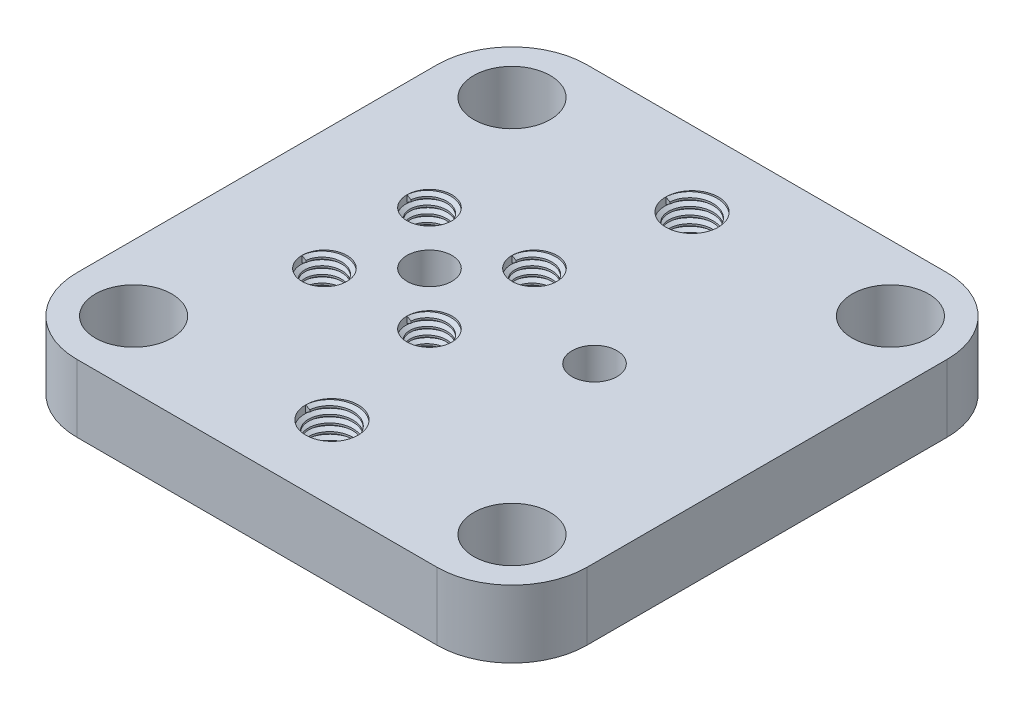
SolidWorks part; units mm, degrees
ref_plane "Front Plane" through (0, 0, 0) normal (0, 0, 1) x (1, 0, 0)
ref_plane "Top Plane" through (0, 0, 0) normal (0, 1, 0) x (1, 0, 0)
ref_plane "Right Plane" through (0, 0, 0) normal (1, 0, 0) x (0, 0, -1)
sketch "Sketch1" plane through (0, 0, 0) normal (0, 1, 0) x (1, 0, 0)
  line L3 (0, 29) -> (0, -29)
  line L4 (0, 0) -> (-29, 0)
  line L5 (-29, -19) -> (-29, 19)
  line L6 (-19, 29) -> (19, 29)
  line L7 (-19, -29) -> (19, -29)
  line L8 (29, -19) -> (29, 19)
  arc A0 (-19, -29) -> (-29, -19) centre (-19, -19) cw
  arc A1 (-29, 19) -> (-19, 29) centre (-19, 19) cw
  arc A2 (19, -29) -> (29, -19) centre (19, -19) ccw
  arc A3 (29, 19) -> (19, 29) centre (19, 19) ccw
  point P4 (0, 0)
  point P9 (-29, -29)
  point P13 (-29, 29)
  dimension "D2" = 10
  dimension "D1" = 29
extrude "Boss-Extrude1" add sketch "Sketch1" along normal blind 9 contours L8 A3 L6 L3 L7 A2 | A0 L7 L3 L4 L5 | A1 L5 L4 L3 L6 region at (14.1788, 0, 0) region at (-14.1788, 0, -14.1788) region at (-14.1788, 0, 14.1788)
sketch "Sketch2" plane through (0, 9, 0) normal (0, 1, 0) x (1, 0, 0)
  line L1 (0, 29) -> (0, 24)
  line L3 (0, 21) -> (-21, 21)
  line L4 (0, 0) -> (0, 21)
  line L5 (0, 0) -> (-4, 0)
  line L10 (-19, 29) -> (19, 29) construction
  circle A0 centre (-11, 0) radius 3
  circle A1 centre (-21, 21) radius 3.5
  circle A2 centre (-21, -21) radius 3.5
  circle A3 centre (21, -21) radius 3.5
  circle A4 centre (21, 21) radius 3.5
  circle A5 centre (11, 0) radius 3
  circle A6 centre (-18, 7) radius 3
  circle A7 centre (-4, 7) radius 3
  circle A8 centre (-18, -7) radius 3
  circle A9 centre (-4, -7) radius 3
  circle A10 centre (0, 24) radius 3.5
  circle A11 centre (0, -24) radius 3.5
  point P4 (0, 0)
  point P10 (0, 29)
  point P12 (0, 21)
  point P23 (-4, 7)
  point P24 (-18, 7)
  point P28 (-4, 0)
extrude "Cut-Extrude1" cut sketch "Sketch2" against normal blind 9 contours A5 | L4 A10 L3 | A9 | A0 | A7 | A6 | A8 | A11 region at (0.011, 9, -24.0516) region at (-11, 9, 0) region at (11, 9, 0) region at (-18, 9, -7) region at (-4, 9, -7) region at (-18, 9, 7) region at (-4, 9, 7)
sketch "Sketch10" plane through (0, 9, 0) normal (0, 1, 0) x (1, 0, 0)
  circle A0 centre (0, 24) radius 3.5
extrude "Cut-Extrude2" cut sketch "Sketch10" against normal blind 9
thread "Thread3" pitch 1 method extrude profile "Thread Profile5" start angle 0, offset 0, length 8, pitch 1, diameter 6
ref_plane "Plane8" through (-7, 9, -7) normal (0, 0, 1) x (-1, 0, 0)
sketch "Thread Profile5" plane through (-7, 9, -7) normal (0, 0, 1) x (-1, 0, 0)
  line L0 (0, 0) -> (0, 1) construction
  line L11 (0, 0) -> (0, 0.875)
  line L12 (0, 0.875) -> (-0.5413, 0.5625)
  line L13 (-0.5413, 0.5625) -> (-0.5413, 0.3125)
  line L15 (-0.5413, 0.3125) -> (0, 0)
  line L17 (-0.5413, 0.4375) -> (0, 0.4375) construction
  point P2 (0, 0)
  dimension "Pitch" = 1
  dimension "Profile_Angle" = 60
  dimension "Profile_Land" = 0.25
  dimension "Profile_Height" = 0.5413
thread "Thread4" pitch 1 method extrude profile "Thread Profile6" start angle 0, offset 0, length 8, pitch 1, diameter 6
ref_plane "Plane9" through (-21, 9, -7) normal (0, 0, 1) x (-1, 0, 0)
sketch "Thread Profile6" plane through (-21, 9, -7) normal (0, 0, 1) x (-1, 0, 0)
  line L0 (0, 0) -> (0, 1) construction
  line L11 (0, 0) -> (0, 0.875)
  line L12 (0, 0.875) -> (-0.5413, 0.5625)
  line L13 (-0.5413, 0.5625) -> (-0.5413, 0.3125)
  line L15 (-0.5413, 0.3125) -> (0, 0)
  line L17 (-0.5413, 0.4375) -> (0, 0.4375) construction
  point P2 (0, 0)
  dimension "Pitch" = 1
  dimension "Profile_Angle" = 60
  dimension "Profile_Land" = 0.25
  dimension "Profile_Height" = 0.5413
thread "Thread5" pitch 1 method extrude profile "Thread Profile7" start angle 0, offset 0, length 8, pitch 1, diameter 6
ref_plane "Plane10" through (-21, 9, 7) normal (0, 0, 1) x (-1, 0, 0)
sketch "Thread Profile7" plane through (-21, 9, 7) normal (0, 0, 1) x (-1, 0, 0)
  line L0 (0, 0) -> (0, 1) construction
  line L11 (0, 0) -> (0, 0.875)
  line L12 (0, 0.875) -> (-0.5413, 0.5625)
  line L13 (-0.5413, 0.5625) -> (-0.5413, 0.3125)
  line L15 (-0.5413, 0.3125) -> (0, 0)
  line L17 (-0.5413, 0.4375) -> (0, 0.4375) construction
  point P2 (0, 0)
  dimension "Pitch" = 1
  dimension "Profile_Angle" = 60
  dimension "Profile_Land" = 0.25
  dimension "Profile_Height" = 0.5413
thread "Thread6" pitch 1 method extrude profile "Thread Profile8" start angle 0, offset 0, length 8, pitch 1, diameter 6
ref_plane "Plane11" through (-7, 9, 7) normal (0, 0, 1) x (-1, 0, 0)
sketch "Thread Profile8" plane through (-7, 9, 7) normal (0, 0, 1) x (-1, 0, 0)
  line L0 (0, 0) -> (0, 1) construction
  line L11 (0, 0) -> (0, 0.875)
  line L12 (0, 0.875) -> (-0.5413, 0.5625)
  line L13 (-0.5413, 0.5625) -> (-0.5413, 0.3125)
  line L15 (-0.5413, 0.3125) -> (0, 0)
  line L17 (-0.5413, 0.4375) -> (0, 0.4375) construction
  point P2 (0, 0)
  dimension "Pitch" = 1
  dimension "Profile_Angle" = 60
  dimension "Profile_Land" = 0.25
  dimension "Profile_Height" = 0.5413
thread "Thread9" pitch 1 method extrude profile "Thread Profile11" start angle 0, offset 0, length 8, pitch 1, diameter 7
ref_plane "Plane14" through (-3.5, 9, -24) normal (0, 0, 1) x (-1, 0, 0)
sketch "Thread Profile11" plane through (-3.5, 9, -24) normal (0, 0, 1) x (-1, 0, 0)
  line L0 (0, 0) -> (0, 1) construction
  line L11 (0, 0) -> (0, 0.875)
  line L12 (0, 0.875) -> (-0.5413, 0.5625)
  line L13 (-0.5413, 0.5625) -> (-0.5413, 0.3125)
  line L15 (-0.5413, 0.3125) -> (0, 0)
  line L17 (-0.5413, 0.4375) -> (0, 0.4375) construction
  point P2 (0, 0)
  dimension "Pitch" = 1
  dimension "Profile_Angle" = 60
  dimension "Profile_Land" = 0.25
  dimension "Profile_Height" = 0.5413
thread "Thread12" pitch 1 method extrude profile "Thread Profile14" start angle 0, offset 0, length 8, pitch 1, diameter 7
ref_plane "Plane17" through (-3.5, 9, 24) normal (0, 0, 1) x (-1, 0, 0)
sketch "Thread Profile14" plane through (-3.5, 9, 24) normal (0, 0, 1) x (-1, 0, 0)
  line L0 (0, 0) -> (0, 1) construction
  line L11 (0, 0) -> (0, 0.875)
  line L12 (0, 0.875) -> (-0.5413, 0.5625)
  line L13 (-0.5413, 0.5625) -> (-0.5413, 0.3125)
  line L15 (-0.5413, 0.3125) -> (0, 0)
  line L17 (-0.5413, 0.4375) -> (0, 0.4375) construction
  point P2 (0, 0)
  dimension "Pitch" = 1
  dimension "Profile_Angle" = 60
  dimension "Profile_Land" = 0.25
  dimension "Profile_Height" = 0.5413
sketch "Sketch11" plane through (0, 9, 0) normal (0, 1, 0) x (1, 0, 0)
  line L0 (0, 0) -> (25.22, 0)
  line L3 (25.22, 0) -> (25.22, 25.22)
  line L4 (0, 0) -> (0, 39.5098)
  line L5 (0, 0) -> (-34, 0)
  line L6 (0, 34) -> (0, -34)
  line L7 (-34, 24) -> (-34, -24)
  line L8 (-24, -34) -> (24, -34)
  line L9 (-24, 34) -> (24, 34)
  line L10 (34, 24) -> (34, -24)
  line L11 (0, 0) -> (29, 0)
  line L12 (29, -19) -> (29, 19) construction
  line L13 (29, -19) -> (29, 19)
  line L14 (19, 29) -> (-19, 29)
  line L15 (19, -29) -> (-19, -29)
  line L16 (-29, -19) -> (-29, 19)
  arc A4 (-34, -24) -> (-24, -34) centre (-24, -24) ccw
  arc A5 (-34, 24) -> (-24, 34) centre (-24, 24) cw
  arc A6 (34, 24) -> (24, 34) centre (24, 24) ccw
  arc A7 (34, -24) -> (24, -34) centre (24, -24) cw
  arc A8 (19, 29) -> (29, 19) centre (19, 19) cw
  arc A9 (19, -29) -> (29, -19) centre (19, -19) ccw
  arc A10 (-19, -29) -> (-29, -19) centre (-19, -19) cw
  arc A11 (-19, 29) -> (-29, 19) centre (-19, 19) ccw
  point P34 (0, -29)
  point P39 (0, 29)
  line M33 (-29, 19) -> (-29, -19)
  arc M34 (-29, -19) -> (-19, -29) centre (-19, -19) ccw
  line M35 (-19, -29) -> (19, -29)
  arc M36 (19, -29) -> (29, -19) centre (19, -19) ccw
  line M37 (29, -19) -> (29, 19)
  arc M38 (29, 19) -> (19, 29) centre (19, 19) ccw
  line M39 (19, 29) -> (-19, 29)
  arc M40 (-19, 29) -> (-29, 19) centre (-19, 19) ccw
  dimension "D1" = 10
  dimension "D2" = 10
extrude "Boss-Extrude2" add sketch "Sketch11" against normal blind 9 contours A5 L7 L5 L4 L9 M33 M40 M39 | A7 L10 A6 L9 L4 L6 L8 M39 M38 M37 M36 M35 | L7 A4 L8 L6 L5 M35 M34 M33 region at (-9.5, 9, -29.4808) region at (0.7603, 9, -31.5) region at (-29.4808, 9, 9.5)
sketch "Sketch12" plane through (0, 9, 0) normal (0, 1, 0) x (1, 0, 0)
  line L0 (0, 0) -> (25.22, 0)
  line L1 (0, 0) -> (0, 16.9497)
  line L2 (0, 29) -> (0, -29) construction
  circle A0 centre (25.22, 25.22) radius 5.1
  circle A1 centre (25.22, -25.22) radius 5.1
  circle A2 centre (-25.22, -25.22) radius 5.1
  circle A3 centre (-25.22, 25.22) radius 5.1
extrude "Cut-Extrude3" cut sketch "Sketch12" against normal blind 9 contours A3 | A0 | A2 | A1 region at (25.22, 9, -25.22) region at (25.22, 9, 25.22) region at (-25.22, 9, 25.22) region at (-25.22, 9, -25.22)
ref_axis "Axis1" through (25.22, -6.0099, -25.22) along (0, 1, 0)
ref_axis "Axis2" through (25.22, -6.995, 25.22) along (0, 1, 0)
ref_axis "Axis3" through (-25.22, -6.7873, 25.22) along (0, 1, 0)
ref_axis "Axis4" through (-25.22, -9.8618, -25.22) along (0, 1, 0)
